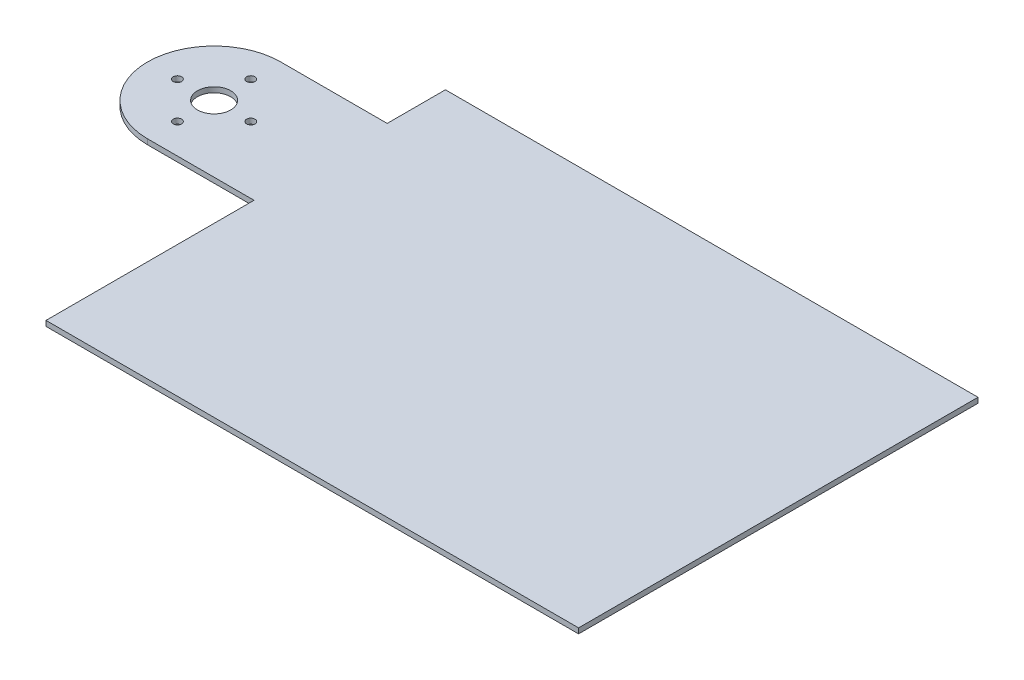
SolidWorks part; units mm, degrees
ref_plane "Front Plane" through (0, 0, 0) normal (0, 0, 1) x (1, 0, 0)
ref_plane "Top Plane" through (0, 0, 0) normal (0, 1, 0) x (1, 0, 0)
ref_plane "Right Plane" through (0, 0, 0) normal (1, 0, 0) x (0, 0, -1)
sketch "Sketch1" plane through (0, 0, 0) normal (0, 1, 0) x (1, 0, 0)
  line L0 (0, 12.7) -> (20.32, 12.7)
  line L2 (20.32, -12.7) -> (0, -12.7)
  line L3 (20.32, 12.7) -> (20.32, 23.8125)
  line L4 (20.32, -52.3875) -> (121.92, -52.3875)
  line L5 (20.32, -52.3875) -> (20.32, -12.7)
  line L6 (20.32, 23.8125) -> (121.92, 23.8125)
  line L7 (121.92, -52.3875) -> (121.92, 23.8125)
  arc A0 (0, 12.7) -> (0, -12.7) centre (0, 0) ccw
  circle A1 centre (7, 0) radius 0.8
  circle A2 centre (0, -7) radius 0.8
  circle A3 centre (-7, 0) radius 0.8
  circle A4 centre (0, 7) radius 0.8
  circle A5 centre (0, 0) radius 3.175
  point P21 (0, 0)
  dimension "D1" = 12.7
  dimension "D3" = 1.6
  dimension "D9" = 6.35
  dimension "D2" = 7
  dimension "D5" = 20.32
  dimension "D6" = 101.6
  dimension "D7" = 76.2
  dimension "D8" = 23.8125
  dimension "D4" = 4
extrude "Boss-Extrude1" add sketch "Sketch1" along normal mid plane 1
equation "\"D2@Sketch1\"=7mm"
equation "\"D3@Sketch1\"=1.6mm"
equation "\"D5@Sketch1\"=0.8"
equation "\"D1@Boss-Extrude1\"=1mm"
